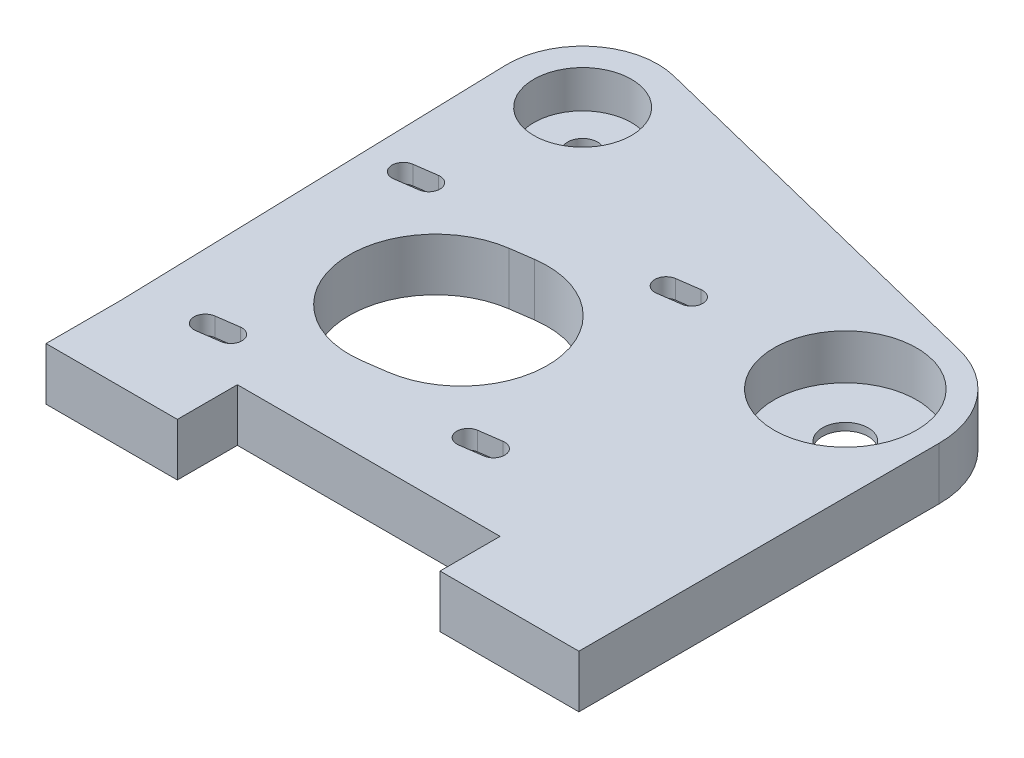
SolidWorks part; units mm, degrees
note: The reader was unsure of these and kept them because the rebuilt part matched: shared geometry of "Sketch2<4>", "Sketch2<5>", "Sketch2<6>".
ref_plane "Front" through (0, 0, 0) normal (0, 0, 1) x (1, 0, 0)
ref_plane "Top" through (0, 0, 0) normal (0, 1, 0) x (1, 0, 0)
ref_plane "Right" through (0, 0, 0) normal (1, 0, 0) x (0, 0, -1)
sketch "Sketch2" plane through (0, 0, 0) normal (0, 1, 0) x (1, 0, 0)
  line L0 (-101.1698, 0) -> (151.9116, 0) construction
  line L1 (0, 0) -> (133.1277, 18.7099) construction
  line L2 (52.9793, 7.4458) -> (55.9501, 7.8633) construction
  line L3 (51.3789, 18.8338) -> (54.3497, 19.2514)
  line L4 (54.5798, -3.9423) -> (57.5506, -3.5248)
  line L5 (50.7009, 34.4356) -> (58.2286, -19.1265) construction
  line L6 (22.0885, -12.548) -> (91.1553, -2.8413) construction
  line L11 (17.7742, 18.1503) -> (86.8409, 27.857) construction
  line L12 (66.1713, 24.9521) -> (69.1421, 25.3696) construction
  line L13 (65.7886, 27.6753) -> (68.7594, 28.0929)
  line L14 (65.9626, 26.4375) -> (68.9334, 26.855)
  line L15 (66.3801, 23.4667) -> (69.3509, 23.8842)
  line L16 (66.554, 22.2289) -> (69.5248, 22.6464)
  line L17 (70.4857, -5.7462) -> (73.4565, -5.3287) construction
  line L18 (70.6944, -7.2316) -> (73.6652, -6.8141)
  line L19 (70.2769, -4.2608) -> (73.2477, -3.8433)
  line L20 (70.8684, -8.4694) -> (73.8392, -8.0519)
  line L21 (70.103, -3.023) -> (73.0738, -2.6055)
  line L22 (42.7582, -9.6431) -> (39.7874, -10.0606) construction
  line L23 (42.9669, -11.1285) -> (39.9961, -11.546)
  line L24 (42.5494, -8.1577) -> (39.5786, -8.5752)
  line L25 (38.4438, 21.0553) -> (35.473, 20.6377) construction
  line L26 (38.235, 22.5407) -> (35.2642, 22.1231)
  line L27 (38.6526, 19.5699) -> (35.6818, 19.1523)
  line L28 (38.0611, 23.7785) -> (35.0903, 23.361)
  line L29 (38.8265, 18.332) -> (35.8557, 17.9145)
  line L30 (42.3754, -6.9198) -> (39.4046, -7.3373)
  line L31 (43.1409, -12.3663) -> (40.1701, -12.7838)
  line L34 (90.012, 24.9921) -> (40.012, 24.9921) construction
  line L35 (40.012, 24.9921) -> (40.012, 39.9921) construction
  line L36 (54.4647, 7.6545) -> (99.593, 29.6651) construction
  line L39 (102.512, 24.9921) -> (102.512, -23.0079)
  line L40 (102.512, -23.0079) -> (84.012, -23.0079)
  line L41 (42.4235, 49.697) -> (93.0264, 37.1232)
  line L42 (31.512, -23.0079) -> (31.512, -13.0079)
  line L43 (31.512, -13.0079) -> (30.0161, 39.7084)
  line L44 (49.012, -23.0079) -> (49.012, -15.0079)
  line L45 (49.012, -15.0079) -> (84.012, -15.0079)
  line L46 (84.012, -15.0079) -> (84.012, -23.0079)
  line L47 (49.012, -23.0079) -> (31.512, -23.0079)
  arc A1 (51.3789, 18.8338) -> (54.5798, -3.9423) centre (52.9793, 7.4458) ccw
  arc A2 (57.5506, -3.5248) -> (54.3497, 19.2514) centre (55.9501, 7.8633) ccw
  arc A3 (65.9626, 26.4375) -> (66.3801, 23.4667) centre (66.1713, 24.9521) ccw
  arc A4 (69.3509, 23.8842) -> (68.9334, 26.855) centre (69.1421, 25.3696) ccw
  arc A5 (69.5248, 22.6464) -> (68.7594, 28.0929) centre (69.1421, 25.3696) ccw
  arc A6 (65.7886, 27.6753) -> (66.554, 22.2289) centre (66.1713, 24.9521) ccw
  arc A7 (70.6944, -7.2316) -> (70.2769, -4.2608) centre (70.4857, -5.7462) cw
  arc A8 (73.2477, -3.8433) -> (73.6652, -6.8141) centre (73.4565, -5.3287) cw
  arc A9 (73.0738, -2.6055) -> (73.8392, -8.0519) centre (73.4565, -5.3287) cw
  arc A10 (70.8684, -8.4694) -> (70.103, -3.023) centre (70.4857, -5.7462) cw
  arc A11 (42.9669, -11.1285) -> (42.5494, -8.1577) centre (42.7582, -9.6431) ccw
  arc A12 (39.5786, -8.5752) -> (39.9961, -11.546) centre (39.7874, -10.0606) ccw
  arc A13 (38.235, 22.5407) -> (38.6526, 19.5699) centre (38.4438, 21.0553) cw
  arc A14 (35.6818, 19.1523) -> (35.2642, 22.1231) centre (35.473, 20.6377) cw
  arc A15 (35.8557, 17.9145) -> (35.0903, 23.361) centre (35.473, 20.6377) cw
  arc A16 (38.0611, 23.7785) -> (38.8265, 18.332) centre (38.4438, 21.0553) cw
  arc A17 (39.4046, -7.3373) -> (40.1701, -12.7838) centre (39.7874, -10.0606) ccw
  arc A18 (43.1409, -12.3663) -> (42.3754, -6.9198) centre (42.7582, -9.6431) ccw
  circle A20 centre (90.012, 24.9921) radius 9.5
  arc A21 (102.512, 24.9921) -> (93.0264, 37.1232) centre (90.012, 24.9921) ccw
  circle A22 centre (40.012, 39.9921) radius 6.5
  arc A25 (42.4235, 49.697) -> (30.0161, 39.7084) centre (40.012, 39.9921) ccw
  circle A26 centre (90.012, 24.9921) radius 3.05
  circle A27 centre (40.012, 39.9921) radius 2
  point P7 (52.9793, 7.4458)
  point P8 (55.9501, 7.8633)
  point P11 (54.4647, 7.6545)
  point P16 (41.2728, -9.8518)
  point P19 (54.4647, 7.6545)
  point P21 (71.9711, -5.5375)
  point P23 (56.6219, -7.6946)
  point P25 (36.9584, 20.8465)
  point P28 (67.6567, 25.1609)
  point P32 (67.6567, 25.1609)
  point P43 (71.9711, -5.5375)
  point P56 (41.2728, -9.8518)
  point P63 (36.9584, 20.8465)
  point P88 (90.012, 24.9921)
  dimension "D2" = 3
  dimension "D9" = 18
  dimension "D10" = 39.55
  dimension "D13" = 13
  dimension "D14" = 11.5
  dimension "D15" = 2.75
  dimension "D16" = 20
  dimension "D17" = 48
  dimension "D3" = 19
  dimension "D4" = 25
  dimension "D18" = 10
  dimension "D23" = 6.1
  dimension "D24" = 4
  dimension "D1" = 8
  dimension "D5" = 15.5
  dimension "D6" = 15.5
  dimension "D7" = 1.25
  dimension "D8" = 55
  dimension "D11" = 50
  dimension "D12" = 15
  dimension "D19" = 8
  dimension "D20" = 35
  dimension "D21" = 71
  dimension "D22" = 17.5
extrude "Boss-Extrude1" add sketch "Sketch2" along normal blind 7 contours L41 A25 L43 L42 L47 L44 L45 L46 L40 L39 A21 L28 A16 L29 A15 A2 L4 A1 L3 A6 L13 A5 L16 L20 A10 L21 A9 A18 L31 A17 L30 A20 A22 | L13 A6 L16 A5 A4 L15 A3 L14 | L15 A4 L14 A3 | A14 L27 A13 L26 | A16 L28 A15 L29 L27 A14 L26 A13 | L31 A18 L30 A17 A12 L24 A11 L23 | L24 A12 L23 A11 | A8 L19 A7 L18 | A10 L20 A9 L21 L19 A8 L18 A7 | A20 A26 | A22 A27
extrude "Cut-Extrude1" cut sketch "Sketch2<4>" against normal blind 6 from surface at 7 contours A20 starting at face at (71.9711, 7, 5.5375)
sketch "Sketch2<4>" plane through (0, 0, 0) normal (0, 1, 0) x (1, 0, 0) same geometry as "Sketch2"
extrude "Cut-Extrude2" cut sketch "Sketch2<5>" against normal blind 5 from surface at 7 contours A22 starting at face at (90.012, 7, -15.4921)
sketch "Sketch2<5>" plane through (0, 0, 0) normal (0, 1, 0) x (1, 0, 0) same geometry as "Sketch2"
extrude "Cut-Extrude3" cut sketch "Sketch2<6>" along normal blind 4.5 contours L13 A5 L16 A6 | L28 A15 L29 A16 | L30 A17 L31 A18 | L21 A9 L20 A10
sketch "Sketch2<6>" plane through (0, 0, 0) normal (0, 1, 0) x (1, 0, 0) same geometry as "Sketch2"
